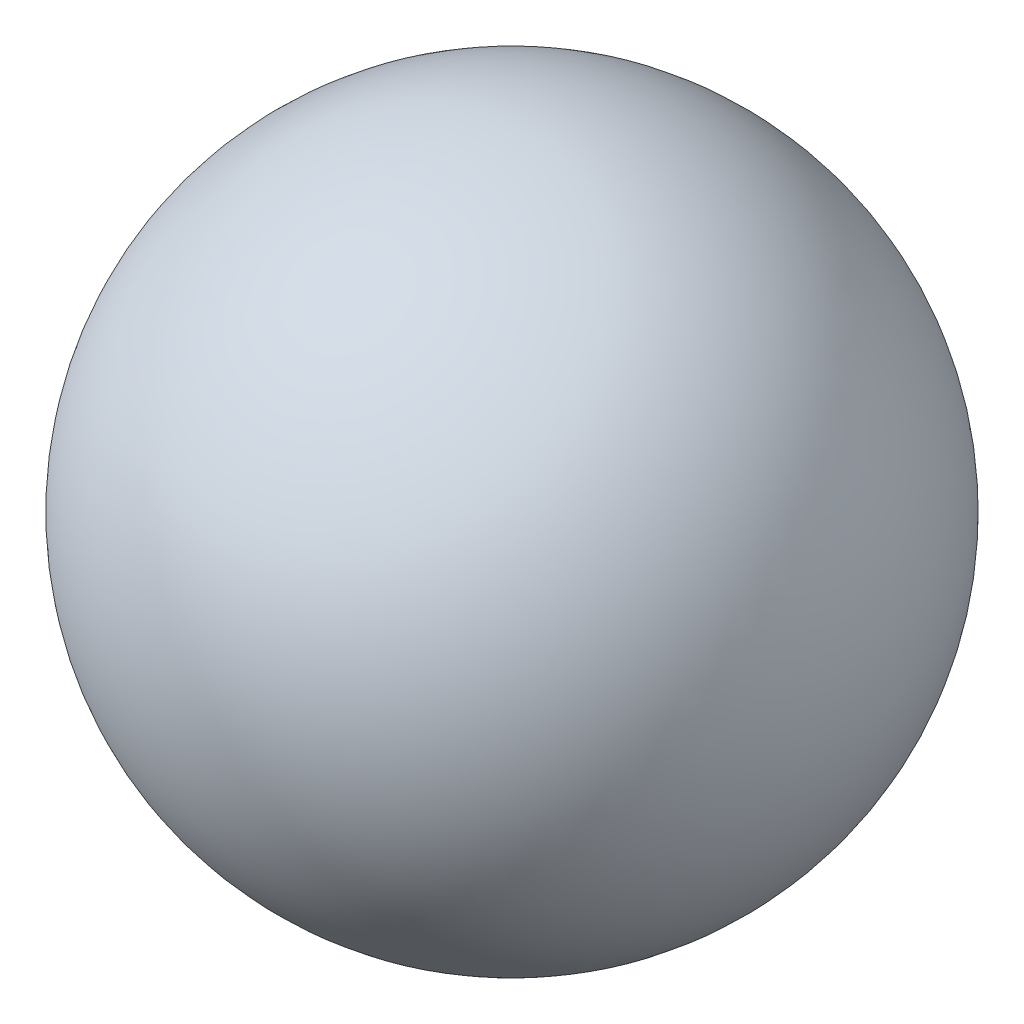
SolidWorks part; units mm, degrees
ref_plane "Front Plane" through (0, 0, 0) normal (0, 0, 1) x (1, 0, 0)
ref_plane "Top Plane" through (0, 0, 0) normal (0, 1, 0) x (1, 0, 0)
ref_plane "Right Plane" through (0, 0, 0) normal (1, 0, 0) x (0, 0, -1)
sketch "Sketch1" plane through (0, 0, 0) normal (0, 0, 1) x (1, 0, 0)
  line L0 (0, -20) -> (0, 20) construction
  circle A0 centre (0, 0) radius 20
  dimension "D1" = 40
revolve "Revolve1" add sketch "Sketch1" angle 360 about L0 region at (-8.4883, 0, 0)
